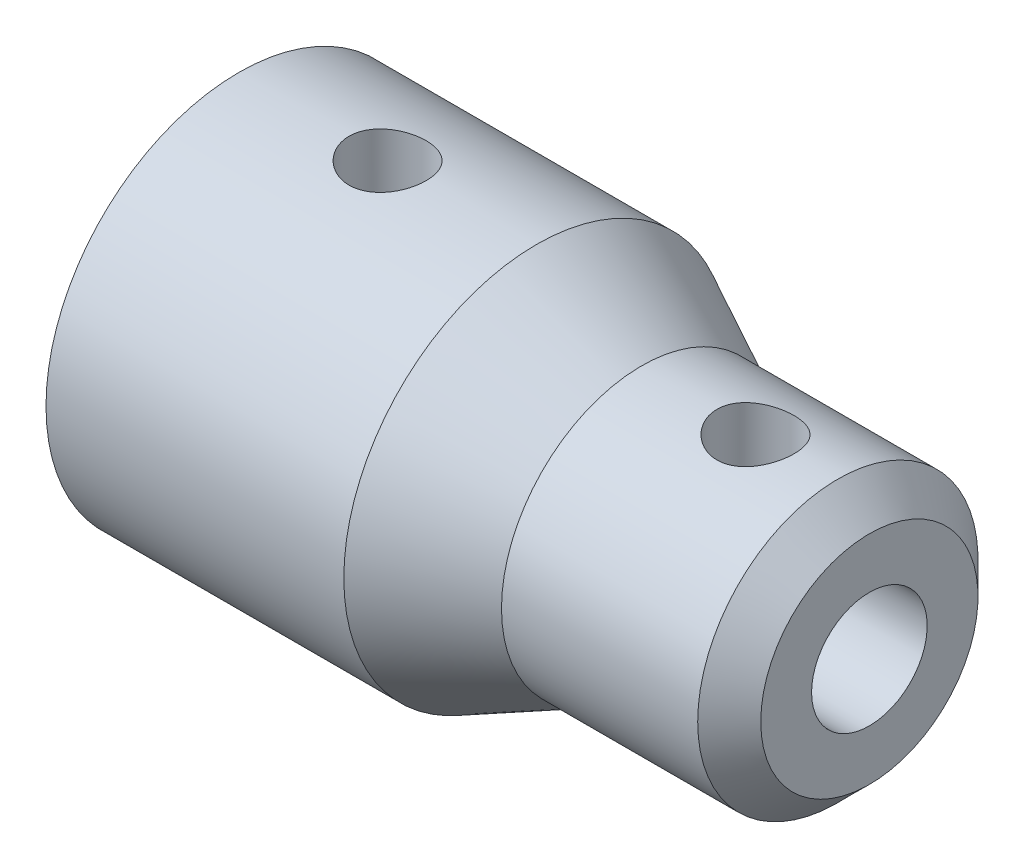
SolidWorks part; units mm, degrees
material "PLA"
ref_plane "Front Plane" through (0, 0, 0) normal (0, 0, 1) x (1, 0, 0)
ref_plane "Top Plane" through (0, 0, 0) normal (0, 1, 0) x (1, 0, 0)
ref_plane "Right Plane" through (0, 0, 0) normal (1, 0, 0) x (0, 0, -1)
sketch "Sketch1" plane through (0, 0, 0) normal (0, 1, 0) x (1, 0, 0)
  line L0 (0, 0) -> (50114.9151, 0) construction
  line L1 (0, -1002.2983) -> (0, 0) construction
  line L2 (-10.795, 3.4036) -> (0, 3.4036)
  line L3 (0, 6.985) -> (3.81, 5.08)
  line L4 (-10.795, 3.4036) -> (-10.795, 6.985)
  line L5 (-10.795, 6.985) -> (0, 6.985)
  line L8 (12.065, 5.08) -> (12.065, 2.0955)
  line L9 (0, 3.4036) -> (0, 50114.9151) construction
  line L10 (0, 3.4036) -> (1.905, 2.0955)
  line L11 (1.905, 2.0955) -> (12.065, 2.0955)
  line L12 (3.81, 5.08) -> (12.065, 5.08)
  line L13 (0.4092, 3.4036) -> (50000.4092, 3.4036) construction
  line L14 (0, 6.985) -> (50000, 6.985) construction
  dimension "D1" = 4.191
  dimension "D2" = 6.8072
  dimension "D3" = 1.905
  dimension "D4" = 13.97
  dimension "D5" = 10.16
  dimension "D6" = 22.86
  dimension "D7" = 10.795
  dimension "D8" = 3.81
revolve "Revolve1" add sketch "Sketch1" angle 360 about L0
sketch "Sketch2" plane through (0, 0, 0) normal (0, 1, 0) x (1, 0, 0)
  line L0 (0, 0) -> (50000, 0) construction
  line L1 (0, 6.985) -> (-10.795, 6.985) construction
  line L2 (-5.3975, 6.985) -> (-5.3975, 0) construction
  line L3 (7.9375, 5.08) -> (7.9375, 0) construction
  line L4 (12.065, 5.08) -> (3.81, 5.08) construction
  circle A0 centre (-5.3975, 0) radius 1.397
  circle A1 centre (7.9375, 0) radius 1.397
  dimension "D1" = 2.794
  dimension "D2" = 2.794
extrude "Cut-Extrude1" cut sketch "Sketch2" along normal through all
pattern_circular "CirPattern1" count 2 every 90 about axis through (-10.795, 0, 0) along (-1, 0, 0) of "Cut-Extrude1"
chamfer "Chamfer1" distance 1.143 angle 45 1 edges at (12.065, 0, 5.08)
equation "\"D2@Sketch2\"=\"D1@Sketch2\""
